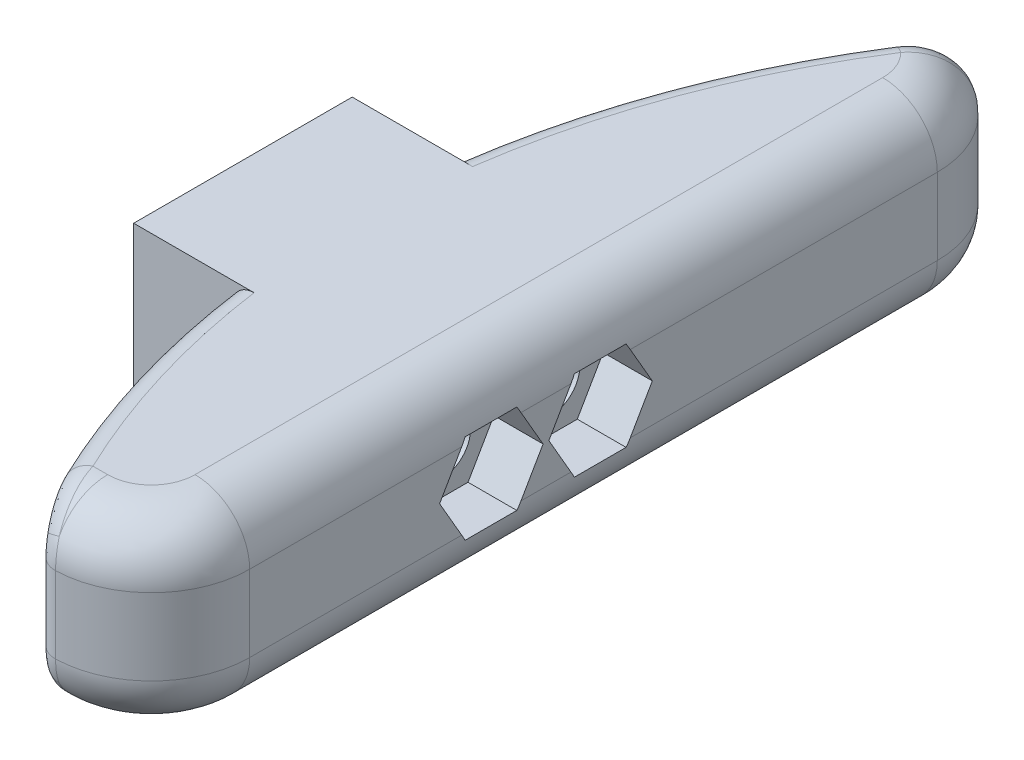
SolidWorks part; units mm, degrees
ref_plane "Alzado" through (0, 0, 0) normal (0, 0, 1) x (1, 0, 0)
ref_plane "Planta" through (0, 0, 0) normal (0, 1, 0) x (1, 0, 0)
ref_plane "Vista lateral" through (0, 0, 0) normal (1, 0, 0) x (0, 0, -1)
sketch "Croquis1" plane through (0, 0, 0) normal (0, 1, 0) x (1, 0, 0)
  line L0 (0, 0) -> (0, 40) construction
  line L2 (0, 0) -> (0, -40) construction
  line L5 (-71.2128, -14.2252) -> (-80.2128, -14.2252)
  line L7 (-71.2128, 5.7748) -> (-80.2128, 5.7748)
  line L8 (-80.2128, -14.2252) -> (-80.2128, 5.7748)
  line L9 (-71.3201, -0.3448) -> (-80.2128, 5.7748) construction
  line L10 (-71.3201, -0.3448) -> (-80.2128, -14.2252) construction
  line L15 (-57.4777, 39.6552) -> (-52.4777, 39.6552)
  line L30 (-52.4777, 39.6552) -> (-52.4777, -40.3448)
  line L31 (-52.4777, -40.3448) -> (-62.4777, -40.3448)
  arc A1 (-57.4777, 39.6552) -> (-71.2128, 5.7748) centre (2.1084, -4.2252) ccw
  arc A4 (-71.2128, -14.2252) -> (-62.4777, -40.3448) centre (2.1084, -4.2252) ccw
  point P1 (-71.3201, -0.3448)
  dimension "D1" = 40
  dimension "D2" = 40
  dimension "D4" = 40
  dimension "D5" = 9
  dimension "D6" = 20
  dimension "D3" = 40
  dimension "D7" = 5
  dimension "D8" = 10
extrude "Saliente-Extruir1" add sketch "Croquis1" along normal blind 17
sketch "Croquis3" plane through (-80.2128, 0, 0) normal (-1, 0, 0) x (0, 0, 1)
  line L0 (-5.7748, 8.5) -> (14.2252, 8.5) construction
  line L1 (-5.7748, 17) -> (-5.7748, 0) construction
  line L2 (14.2252, 17) -> (14.2252, 0) construction
  line L3 (-5.7748, 17) -> (-5.7748, 0) construction
  circle A0 centre (-0.7748, 8.5) radius 2.6
  circle A1 centre (9.2252, 8.5) radius 2.6
  dimension "D1" = 5.2
  dimension "D3" = 5.2
  dimension "D2" = 5
  dimension "D4" = 5
extrude "Cortar-Extruir1" cut sketch "Croquis3" against normal through all
fillet "Redondeo1" radius 9 2 edges at (-52.4777, 8.5, 40.3448) (-52.4777, 8.5, -39.6552)
fillet "Redondeo2" radius 5 8 edges at (-61.9777, 17, 40.3448) (-55.1138, 17, 37.7088) (-53.8292, 17, -36.3363) (-61.9777, 0, 40.3448) (-55.1138, 0, 37.7088) (-53.8292, 0, -36.3363) (-52.4777, 17, -0.124) (-52.4777, 0, -0.124)
fillet "Redondeo3" radius 2 10 edges at (-67.3901, 17, -21.1904) (-68.9108, 17, 25.0161) (-62.9642, 14.8385, 39.461) (-62.4777, 8.5, 40.3448) (-63.3464, 1.3348, 38.7457) (-67.3901, 0, -21.1904) (-68.9108, 0, 25.0161) (-58.5385, 15.8333, -38.177) (-57.4777, 8.5, -39.6552) (-58.1136, 1.9139, -38.7784)
sketch "Croquis4" plane through (-52.4777, 0, 0) normal (1, 0, 0) x (0, 0, -1)
  line L1 (-3.9595, 8.5) -> (-1.5924, 4.4)
  line L2 (-1.5924, 4.4) -> (3.1419, 4.4)
  line L3 (3.1419, 4.4) -> (5.509, 8.5)
  line L4 (5.509, 8.5) -> (3.1419, 12.6)
  line L5 (3.1419, 12.6) -> (-1.5924, 12.6)
  line L6 (-1.5924, 12.6) -> (-3.9595, 8.5)
  line L7 (-4.491, 8.5) -> (-6.8581, 12.6)
  line L8 (-6.8581, 12.6) -> (-11.5924, 12.6)
  line L9 (-11.5924, 12.6) -> (-13.9595, 8.5)
  line L10 (-13.9595, 8.5) -> (-11.5924, 4.4)
  line L11 (-11.5924, 4.4) -> (-6.8581, 4.4)
  line L12 (-6.8581, 4.4) -> (-4.491, 8.5)
  circle A0 centre (0.7748, 8.5) radius 4.1 construction
  circle A1 centre (-9.2252, 8.5) radius 4.1 construction
  dimension "D1" = 8.2
  dimension "D2" = 8.2
extrude "Cortar-Extruir2" cut sketch "Croquis4" against normal blind 4.5
